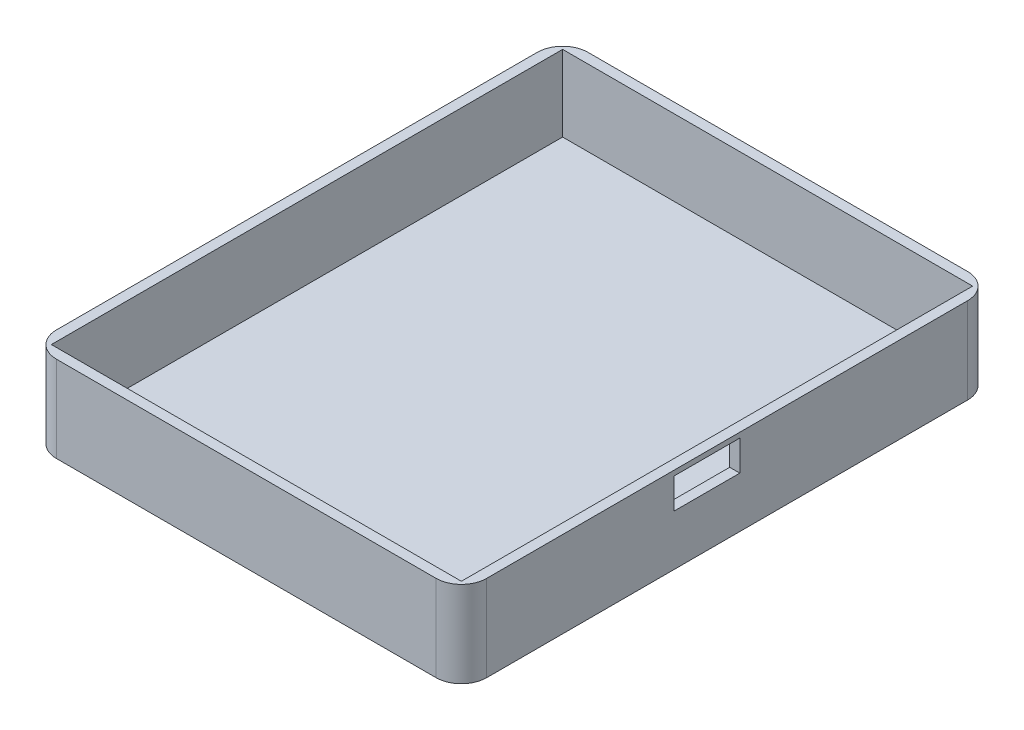
SolidWorks part; units mm, degrees
ref_plane "Front Plane" through (0, 0, 0) normal (0, 0, 1) x (1, 0, 0)
ref_plane "Top Plane" through (0, 0, 0) normal (0, 1, 0) x (1, 0, 0)
ref_plane "Right Plane" through (0, 0, 0) normal (1, 0, 0) x (0, 0, -1)
sketch "Sketch1" plane through (0, 0, 0) normal (0, 1, 0) x (1, 0, 0)
  line L1 (-42.5, -52.5) -> (42.5, -52.5)
  line L2 (-42.5, -52.5) -> (-42.5, 52.5)
  line L3 (-42.5, 52.5) -> (42.5, 52.5)
  line L4 (42.5, -52.5) -> (42.5, 52.5)
  line L5 (-42.5, -52.5) -> (42.5, 52.5) construction
  line L6 (-42.5, 52.5) -> (42.5, -52.5) construction
  point P0 (0, 0)
  dimension "D1" = 85
  dimension "D2" = 105
extrude "Boss-Extrude1" add sketch "Sketch1" along normal blind 17
shell "Shell1" thickness 2 removed face at (0, 17, 0)
sketch "Sketch3" plane through (42.5, 0, 0) normal (1, 0, 0) x (0, 0, -1)
  line L0 (-52.5, 17) -> (-52.5, 0) construction
  line L1 (-10.5, 10) -> (2.5, 10)
  line L2 (-10.5, 10) -> (-10.5, 16)
  line L3 (-10.5, 16) -> (2.5, 16)
  line L4 (2.5, 10) -> (2.5, 16)
  line L5 (-10.5, 10) -> (2.5, 16) construction
  line L6 (-10.5, 16) -> (2.5, 10) construction
  line L7 (52.5, 17) -> (52.5, 0) construction
  line L8 (-52.5, 17) -> (52.5, 17) construction
  point P0 (-4, 13)
  dimension "D1" = 42
  dimension "D2" = 50
  dimension "D3" = 10
  dimension "D4" = 1
extrude "Cut-Extrude1" cut sketch "Sketch3" against normal blind 10
fillet "Fillet1" radius 5 4 edges at (-42.5, 8.5, -52.5) (42.5, 8.5, -52.5) (42.5, 8.5, 52.5) (-42.5, 8.5, 52.5)
